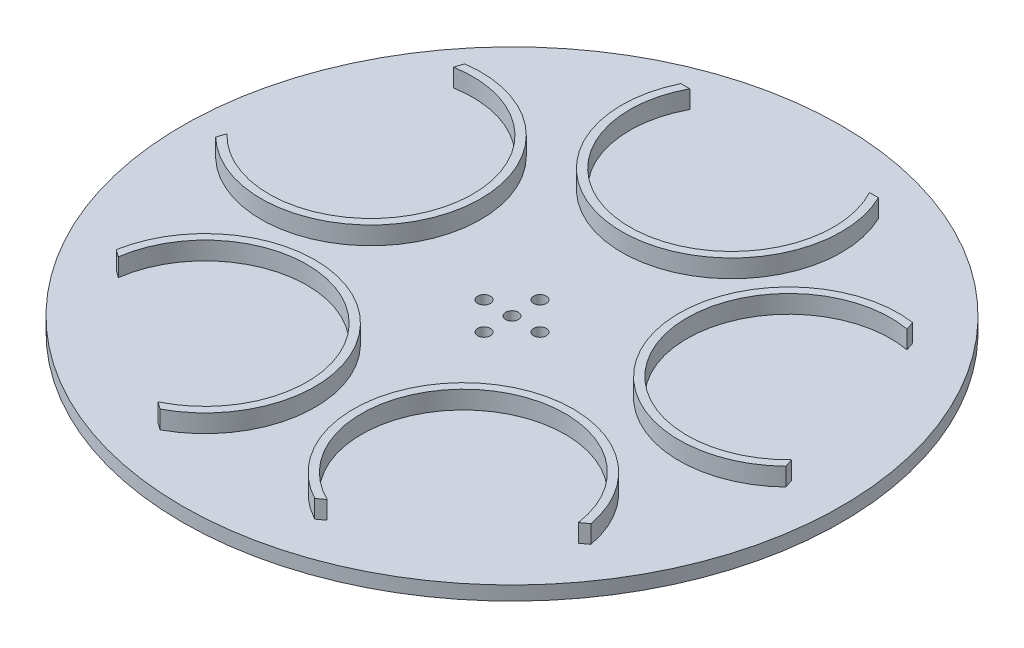
SolidWorks part; units mm, degrees
ref_plane "前视基准面" through (0, 0, 0) normal (0, 0, 1) x (1, 0, 0)
ref_plane "上视基准面" through (0, 0, 0) normal (0, 1, 0) x (1, 0, 0)
ref_plane "右视基准面" through (0, 0, 0) normal (1, 0, 0) x (0, 0, -1)
sketch "草图2" plane through (0, 0, 0) normal (0, 1, 0) x (1, 0, 0)
  line L0 (-22.5, 67) -> (22.5, 67) construction
  line L1 (-22.5, 67) -> (-24.7437, 67)
  line L2 (22.5, 67) -> (24.7437, 67)
  line L3 (56.7679, 42.1029) -> (56.0746, 44.2368)
  line L4 (70.6737, -0.6946) -> (71.367, -2.8285)
  line L5 (57.5845, -40.979) -> (59.3997, -39.6602)
  line L6 (21.1787, -67.4293) -> (19.3635, -68.7481)
  line L7 (-21.1787, -67.4293) -> (-19.3635, -68.7481)
  line L8 (-57.5845, -40.979) -> (-59.3997, -39.6602)
  line L9 (-70.6737, -0.6946) -> (-71.367, -2.8285)
  line L10 (-56.7679, 42.1029) -> (-56.0746, 44.2368)
  line L11 (0, 0) -> (0, 55) construction
  line L12 (0, 0) -> (52.3081, 16.9959) construction
  circle A0 centre (0, 0) radius 82.5
  arc A1 (-24.7437, 67) -> (24.7437, 67) centre (0, 55) ccw
  arc A2 (-22.5, 67) -> (22.5, 67) centre (0, 55) ccw
  arc A3 (0, 82.5) -> (-24.7437, 67) centre (0, 55) ccw construction
  arc A4 (22.5, 67) -> (-22.5, 67) centre (0, 55) ccw construction
  arc A5 (24.7437, 67) -> (0, 82.5) centre (0, 55) ccw construction
  arc A6 (56.0746, 44.2368) -> (71.367, -2.8285) centre (52.3081, 16.9959) ccw
  arc A7 (56.7679, 42.1029) -> (70.6737, -0.6946) centre (52.3081, 16.9959) ccw
  arc A8 (59.3997, -39.6602) -> (19.3635, -68.7481) centre (32.3282, -44.4959) ccw
  arc A9 (57.5845, -40.979) -> (21.1787, -67.4293) centre (32.3282, -44.4959) ccw
  arc A10 (-19.3635, -68.7481) -> (-59.3997, -39.6602) centre (-32.3282, -44.4959) ccw
  arc A11 (-21.1787, -67.4293) -> (-57.5845, -40.979) centre (-32.3282, -44.4959) ccw
  arc A12 (-71.367, -2.8285) -> (-56.0746, 44.2368) centre (-52.3081, 16.9959) ccw
  arc A13 (-70.6737, -0.6946) -> (-56.7679, 42.1029) centre (-52.3081, 16.9959) ccw
  circle A14 centre (0, 0) radius 1.6
  circle A15 centre (0, 7) radius 1.6
  circle A19 centre (7, 0) radius 1.6
  circle A20 centre (0, -7) radius 1.6
  circle A21 centre (-7, 0) radius 1.6
  point P43 (0, 0)
  dimension "D1" = 55
  dimension "165" = 165
  dimension "D2" = 2
  dimension "D7" = 3.2
  dimension "D8" = 3.2
  dimension "D10" = 14
  dimension "D3" = 45
  dimension "D4" = 5
  dimension "D5" = 72
  dimension "D6" = 55
  dimension "D9" = 4
extrude "凸台-拉伸1" add sketch "草图2" along normal blind 3.5 contours A11 L7 A10 L8 | A0 A21 A20 A19 A15 A14 L1 A2 L2 A1 L3 A7 L4 A6 L5 A9 L6 A8 L7 A11 L8 A10 L9 A13 L10 A12 | A2 L1 A1 L2 | A9 L6 A8 L5 | A7 L4 A6 L3 | A12 L10 A13 L9 region at (0, 0, -28.8229) region at (-16.8976, 0, 23.2576) region at (-80.1665, 0, 0)
extrude "凸台-拉伸2" add sketch "草图2<3>" along normal blind 8 contours A9 L5 A8 L6 | A13 L10 A12 L9 | A11 L8 A10 L7 | A7 L4 A6 L3 | A2 L2 A1 L1 region at (16.8976, 0, 23.2576)
sketch "草图2<3>" plane through (0, 0, 0) normal (0, 1, 0) x (1, 0, 0) same geometry as "草图2"
